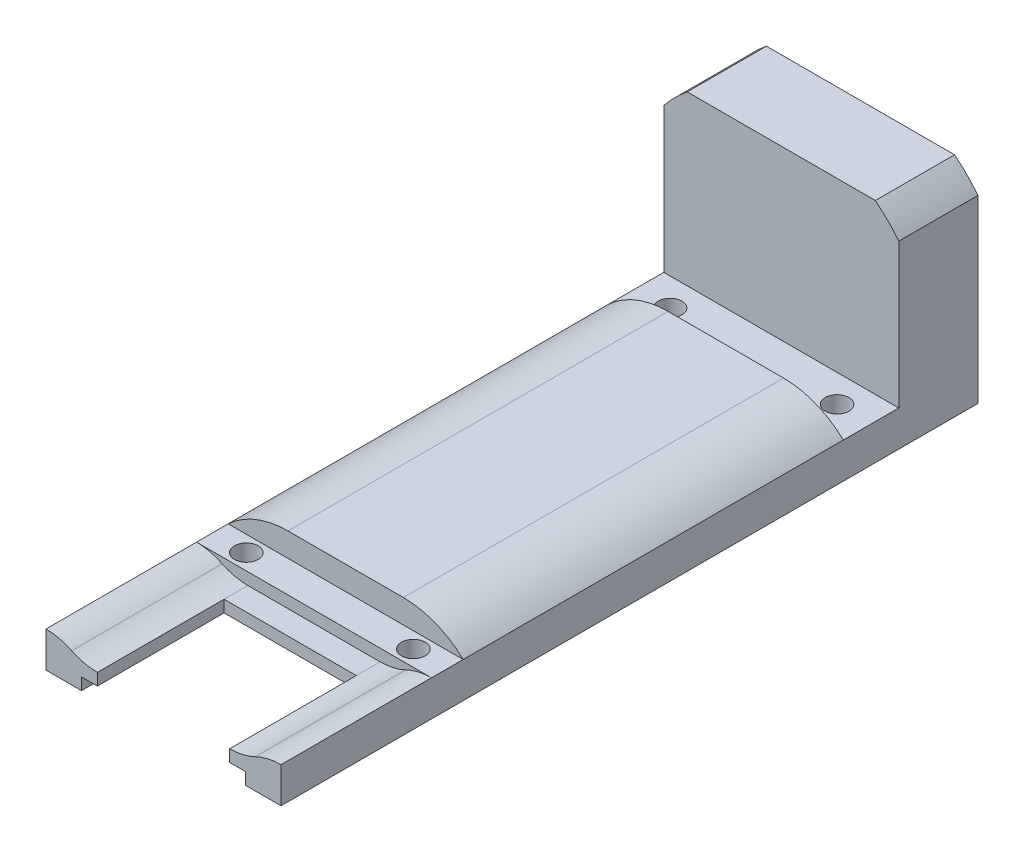
SolidWorks part; units mm, degrees
ref_plane "Front Plane" through (0, 0, 0) normal (0, 0, 1) x (1, 0, 0)
ref_plane "Top Plane" through (0, 0, 0) normal (0, 1, 0) x (1, 0, 0)
ref_plane "Right Plane" through (0, 0, 0) normal (1, 0, 0) x (0, 0, -1)
sketch "Sketch1" plane through (0, 0, 0) normal (0, 0, 1) x (1, 0, 0)
  line L0 (0, 0) -> (0, 29.3495) construction
  line L1 (-14.835, 0) -> (-8.35, 0)
  line L4 (-14.835, 0) -> (-14.835, 4.5)
  line L5 (-14.835, 4.5) -> (-8.35, 4.5)
  line L6 (14.835, 0) -> (14.835, 4.5)
  line L7 (14.835, 0) -> (8.35, 0)
  line L11 (8.35, 4.5) -> (14.835, 4.5)
  line L12 (-8.35, 4.5) -> (8.35, 4.5) construction
  line L13 (-8.35, 0) -> (8.35, 0) construction
  line L14 (-8.35, 0) -> (-8.35, 4.5)
  line L15 (8.35, 0) -> (8.35, 4.5)
  point P10 (0, 21.4888)
  point P13 (0, 23.4888)
  point P16 (0, 0)
  dimension "D1" = 29.67
  dimension "D2" = 6.485
  dimension "D4" = 4.5
extrude "Boss-Extrude1" add sketch "Sketch1" against normal blind 88 contours L14 L5 L4 L1 | L15 L11 L6 L7
sketch "Sketch3" plane through (0, 0, 0) normal (0, 0, 1) x (1, 0, 0)
  line L0 (-14.835, 0) -> (-8.35, 0) construction
  line L1 (-8.35, 0) -> (-10.35, 0)
  line L2 (-8.35, 0) -> (-8.35, 1.5)
  line L3 (-8.35, 1.5) -> (-10.35, 1.5)
  line L4 (-10.35, 0) -> (-10.35, 1.5)
  line L5 (0, 0) -> (0, 11.8528) construction
  line L6 (8.35, 1.5) -> (10.35, 1.5)
  line L7 (10.35, 0) -> (10.35, 1.5)
  line L8 (8.35, 0) -> (10.35, 0)
  line L9 (8.35, 0) -> (8.35, 1.5)
  dimension "D1" = 2
  dimension "D2" = 1.5
extrude "Cut-Extrude2" cut sketch "Sketch3" against normal blind 30
sketch "Sketch4" plane through (0, 0, -88) normal (0, 0, -1) x (-1, 0, 0)
  line L0 (0, 0) -> (0, 13.5394) construction
  line L1 (14.835, 4.5) -> (8.35, 4.5) construction
  line L2 (8.35, 0) -> (8.35, 4.5) construction
  line L3 (8.35, 4.5) -> (10.35, 4.5)
  line L4 (-8.35, 4.5) -> (-8.35, 0)
  line L5 (8.35, 1.5) -> (8.35, 0)
  line L6 (10.35, 1.5) -> (8.35, 1.5)
  line L7 (10.35, 0) -> (10.35, 1.5)
  line L8 (8.35, 0) -> (10.35, 0)
  line L9 (8.35, 4.5) -> (8.35, 0)
  line L11 (10.35, 0) -> (10.35, 4.5)
  line L12 (8.35, 0) -> (10.35, 0)
  line L13 (-8.35, 0) -> (-10.35, 0)
  line L14 (-10.35, 0) -> (-10.35, 4.5)
  line L15 (-8.35, 4.5) -> (-10.35, 4.5)
  dimension "D1" = 0
extrude "Cut-Extrude3" cut sketch "Sketch4" against normal blind 65
sketch "Sketch6" plane through (-10.35, 0, 0) normal (1, 0, 0) x (0, 0, -1)
  line L0 (23, 4.5) -> (0, 4.5) construction
  line L1 (83, 1.5) -> (16, 1.5)
  line L2 (83, 1.5) -> (83, 4.5)
  line L3 (83, 4.5) -> (16, 4.5)
  line L4 (16, 1.5) -> (16, 4.5)
  line L6 (23, 1.5) -> (0, 1.5) construction
  dimension "D1" = 67
extrude "Boss-Extrude2" add sketch "Sketch6" along normal up to surface (20.7 mm away) up to face at (10.35, 2, -37)
sketch "Sketch8" plane through (0, 0, -88) normal (0, 0, -1) x (-1, 0, 0)
  line L0 (-14.835, 0) -> (-14.835, 4.5) construction
  line L3 (-14.835, 0) -> (-14.835, 25.7077)
  line L4 (-14.835, 25.7077) -> (14.835, 25.7077)
  line L6 (-10.35, 1.5) -> (10.35, 1.5) construction
  line L8 (0, 0) -> (0, 41.6063) construction
  line L10 (-10.35, 0) -> (-10.35, 21.2227)
  line L11 (14.835, 0) -> (14.835, 25.7077)
  line L12 (10.35, 0) -> (14.8327, 0)
  line L13 (-14.835, 0) -> (-10.35, 0)
  line L14 (-10.35, 21.2227) -> (10.35, 21.2227)
  line L15 (10.35, 21.2227) -> (10.35, 0)
  arc A1 (14.8327, 22.748) -> (11.874, 25.7067) centre (0, 10.874) ccw construction
  point P26 (0, 25.7077)
  dimension "D1" = 24.2077
  dimension "D2" = 4.485
extrude "Boss-Extrude3" add sketch "Sketch8" against normal blind 5
sketch "Sketch9" plane through (0, 0, -88) normal (0, 0, -1) x (-1, 0, 0)
  line L0 (-15.0091, 25.8817) -> (-15.0091, 22.5273)
  line L7 (-13.437, 24.3096) -> (-15.0091, 25.8817) construction
  line L9 (-15.0091, 25.8817) -> (-11.6546, 25.8817)
  line L10 (-14.835, 25.7077) -> (14.835, 25.7077) construction
  line L11 (0, 0) -> (0, 25.7077) construction
  line L12 (15.0091, 25.8817) -> (15.0091, 22.5273)
  line L13 (15.0091, 25.8817) -> (11.6546, 25.8817)
  arc A1 (-11.6546, 25.8817) -> (-15.0091, 22.5273) centre (-0.0019, 10.8746) ccw
  arc A3 (11.6546, 25.8817) -> (15.0091, 22.5273) centre (0.0019, 10.8746) cw
  dimension "D2" = 19
  dimension "D1" = 45
  dimension "D3" = 3.3544
  dimension "D4" = 0.1741
extrude "Cut-Extrude4" cut sketch "Sketch9" against normal up to surface (5 mm away) up to face at (0, 13.9826, -83)
sketch "Sketch11" plane through (0, 0, -83) normal (0, 0, 1) x (1, 0, 0)
  line L0 (14.835, 4.5) -> (14.835, 22.7481) construction
  line L1 (11.8754, 25.7077) -> (-11.8754, 25.7077) construction
  line L2 (-14.835, 4.5) -> (-14.835, 22.7481) construction
  line L3 (14.835, 4.5) -> (14.835, 22.7481)
  line L4 (11.8754, 25.7077) -> (-11.8754, 25.7077)
  line L5 (-14.835, 4.5) -> (-14.835, 22.7481)
  line L6 (-14.835, 4.5) -> (14.835, 4.5)
  arc A0 (14.835, 22.7481) -> (11.8754, 25.7077) centre (0.0019, 10.8746) ccw construction
  arc A1 (-11.8754, 25.7077) -> (-14.835, 22.7481) centre (-0.0019, 10.8746) ccw construction
  arc A2 (14.835, 22.7481) -> (11.8754, 25.7077) centre (0.0019, 10.8746) ccw
  arc A3 (-11.8754, 25.7077) -> (-14.835, 22.7481) centre (-0.0019, 10.8746) ccw
extrude "Boss-Extrude4" add sketch "Sketch11" along normal blind 5
sketch "Sketch12" plane through (0, 0, -78) normal (0, 0, 1) x (1, 0, 0)
  line L1 (0, 0) -> (0, 30.5664) construction
  line L4 (-14.835, 4.5) -> (-11.835, 7.5)
  line L5 (-11.835, 7.5) -> (11.835, 7.5)
  line L6 (-14.835, 4.5) -> (14.835, 4.5) construction
  line L7 (14.835, 4.5) -> (11.835, 7.5)
  line L8 (-14.835, 4.5) -> (14.835, 4.5)
  line L11 (-14.835, 22.7481) -> (-14.835, 4.5) construction
  point P8 (0, 4.5)
  point P23 (0, 7.5)
  dimension "D1" = 135
  dimension "D2" = 3
extrude "Boss-Extrude5" add sketch "Sketch12" along normal blind 48 from offset 7
sketch "Sketch14" plane through (0, 0, -23) normal (0, 0, 1) x (1, 0, 0)
  line L0 (-11.835, 7.5) -> (-14.835, 4.5) construction
  line L1 (-11.835, 7.5) -> (-14.835, 4.5)
  line L3 (-14.835, 4.5) -> (-8.35, 4.5) construction
  line L5 (0, 0) -> (0, 22.5341) construction
  line L9 (-11.835, 7.5) -> (-10.835, 7.5)
  line L10 (11.835, 7.5) -> (-11.835, 7.5) construction
  line L11 (-10.835, 7.5) -> (-10.835, 4.5)
  line L12 (-14.835, 4.5) -> (-10.835, 4.5)
  line L13 (11.835, 7.5) -> (14.835, 4.5)
  line L14 (11.835, 7.5) -> (10.835, 7.5)
  line L15 (10.835, 7.5) -> (10.835, 4.5)
  line L16 (14.835, 4.5) -> (10.835, 4.5)
  dimension "D1" = 1
extrude "Boss-Extrude6" add sketch "Sketch14" against normal up to surface (48 mm away) up to face at (0, 6, -71)
fillet "Fillet1" radius 11 2 edges at (11.835, 7.5, -47) (-11.835, 7.5, -47)
sketch "Sketch15" plane through (0, 0, -88) normal (0, 0, -1) x (-1, 0, 0)
  line L7 (-11.85, 1.5) -> (11.85, 1.5)
  line L10 (11.85, 22.7227) -> (11.85, 1.5)
  line L11 (-11.85, 22.7227) -> (11.85, 22.7227)
  line L12 (-11.85, 1.5) -> (-11.85, 22.7227)
  line L13 (11.85, 22.7227) -> (11.85, 1.5)
  line L14 (-11.85, 22.7227) -> (11.85, 22.7227)
  line L15 (-11.85, 1.5) -> (-11.85, 22.7227)
  dimension "D1" = 1.5
extrude "Cut-Extrude6" cut sketch "Sketch15" against normal blind 7
sketch "Sketch16" plane through (0, 0, 0) normal (0, 0, 1) x (1, 0, 0)
  line L0 (-8.35, 1.5) -> (-8.35, 4.5) construction
  line L1 (-14.835, 4.5) -> (-8.35, 4.5) construction
  line L2 (-8.35, 3) -> (8.35, 3) construction
  line L3 (-14.835, 4.5) -> (-8.35, 4.5)
  line L4 (-8.35, 4.5) -> (-8.35, 3)
  line L5 (0, 0) -> (0, 6.6203) construction
  line L6 (8.35, 1.5) -> (8.35, 4.5) construction
  line L7 (14.835, 4.5) -> (8.35, 4.5)
  line L8 (8.35, 4.5) -> (8.35, 3)
  line L9 (8.35, 4.5) -> (-8.35, 4.5) construction
  line L10 (-8.35, 3) -> (8.35, 3)
  line L11 (-8.35, 3) -> (-8.35, 4.5)
  line L12 (-8.35, 4.5) -> (8.35, 4.5)
  line L13 (8.35, 3) -> (8.35, 4.5)
  arc A0 (-14.835, 4.5) -> (-11.5925, 3.75) centre (-14.835, -2.8842) cw
  arc A1 (-11.5925, 3.75) -> (-8.35, 3) centre (-8.35, 10.3842) ccw
  arc A2 (14.835, 4.5) -> (11.5925, 3.75) centre (14.835, -2.8842) ccw
  arc A3 (11.5925, 3.75) -> (8.35, 3) centre (8.35, 10.3842) cw
  point P16 (-11.5925, 4.5)
  dimension "D1" = 1.5
extrude "Cut-Extrude7" cut sketch "Sketch16" against normal blind 19 contours A3 A2 L7 L8 | A1 A0 L3 L4 | L11 L10 L13 L12
sketch "Sketch13" plane through (0, 4.5, 0) normal (0, 1, 0) x (1, 0, 0)
  line L0 (0, 16) -> (0, 78) construction
  line L4 (8.35, 16) -> (-8.35, 16) construction
  line L5 (14.835, 71) -> (14.835, 23) construction
  line L6 (11.8754, 78) -> (-11.8754, 78) construction
  line L9 (-14.835, 47) -> (14.835, 47) construction
  arc A7 (11.874, 75.191) -> (11.874, 73.809) centre (10.5427, 74.5) ccw construction
  arc A8 (-11.874, 73.809) -> (-11.874, 75.191) centre (-10.5427, 74.5) ccw construction
  arc A9 (11.874, 21.691) -> (11.874, 20.309) centre (10.5427, 21) ccw construction
  arc A10 (-11.874, 20.309) -> (-11.874, 21.691) centre (-10.5427, 21) ccw construction
  circle A11 centre (10.5427, 74.5) radius 1.5
  circle A12 centre (-10.5427, 74.5) radius 1.5
  circle A13 centre (10.5427, 21) radius 1.5
  circle A14 centre (-10.5427, 21) radius 1.5
  point P23 (0, 47)
extrude "Cut-Extrude5" cut sketch "Sketch13" against normal through all both and the other way through all
